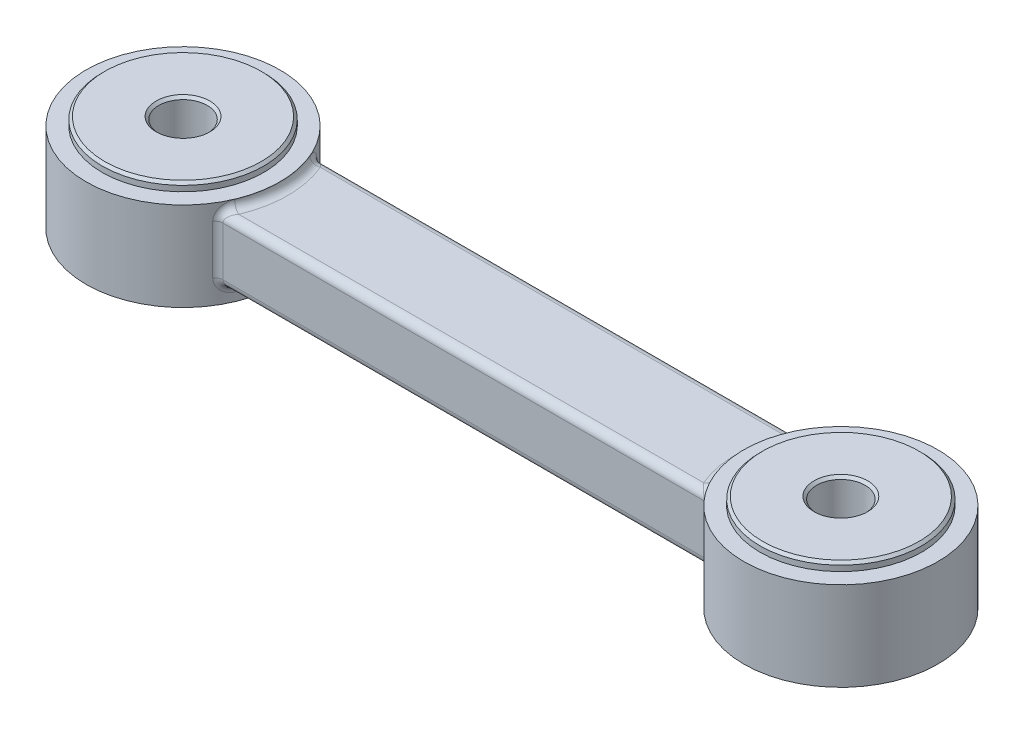
SolidWorks part; units mm, degrees
ref_plane "Front Plane" through (0, 0, 0) normal (0, 0, 1) x (1, 0, 0)
ref_plane "Top Plane" through (0, 0, 0) normal (0, 1, 0) x (1, 0, 0)
ref_plane "Right Plane" through (0, 0, 0) normal (1, 0, 0) x (0, 0, -1)
sketch "Sketch1" plane through (0, 0, 0) normal (0, 1, 0) x (1, 0, 0)
  circle A0 centre (0, 0) radius 19.05
  dimension "D1" = 38.1
extrude "Boss-Extrude2" add sketch "Sketch1" along normal blind 19.05
sketch "Sketch2" plane through (0, 0, 0) normal (0, 1, 0) x (1, 0, 0)
  circle A0 centre (129.2247, 0) radius 19.05
  dimension "D1" = 38.1
extrude "Boss-Extrude3" add sketch "Sketch2" along normal blind 19.05 separate body
sketch "Sketch3" plane through (0, 0, 0) normal (0, 1, 0) x (1, 0, 0)
  line L0 (19.05, 0) -> (110.1747, 0) construction
  line L1 (16.4978, 9.525) -> (112.7269, 9.525)
  line L2 (16.4978, -9.525) -> (112.7269, -9.525)
  circle A0 centre (0, 0) radius 19.05 construction
  circle A1 centre (129.2247, 0) radius 19.05 construction
  circle A3 centre (0, 0) radius 19.05
  arc A4 (16.4978, -9.525) -> (16.4978, 9.525) centre (0, 0) ccw
  circle A5 centre (129.2247, 0) radius 19.05
  arc A6 (112.7269, 9.525) -> (112.7269, -9.525) centre (129.2247, 0) ccw
  dimension "D3" = 9.525
  dimension "D1" = 0
  dimension "D2" = 0
extrude "Boss-Extrude4" add sketch "Sketch3" along normal blind 12.7 from offset 3.175
sketch "Sketch4" plane through (0, 19.05, 0) normal (0, 1, 0) x (1, 0, 0)
  circle A0 centre (0, 0) radius 15.875
  circle A1 centre (129.2247, 0) radius 15.875
  circle A3 centre (0, 0) radius 19.05
  circle A4 centre (0, 0) radius 19.05
  circle A5 centre (129.2247, 0) radius 19.05
  circle A6 centre (129.2247, 0) radius 19.05
  dimension "D1" = 31.75
  dimension "D2" = 31.75
  dimension "D3" = 0
  dimension "D4" = 0
extrude "Cut-Extrude1" cut sketch "Sketch4" against normal blind 1.6002
sketch "Sketch5" plane through (0, 19.05, 0) normal (0, 1, 0) x (1, 0, 0)
  circle A0 centre (0, 0) radius 4.7625
  circle A1 centre (129.2247, 0) radius 4.7625
  dimension "D1" = 9.525
  dimension "D2" = 9.525
extrude "Cut-Extrude2" cut sketch "Sketch5" against normal through all
fillet "Fillet1" radius 1.524 12 edges at (112.7269, 9.525, -9.525) (16.4978, 9.525, -9.525) (110.1747, 3.175, 0) (64.6123, 3.175, -9.525) (19.05, 3.175, 0) (16.4978, 9.525, 9.525) (112.7269, 9.525, 9.525) (64.6123, 3.175, 9.525) (64.6123, 15.875, -9.525) (110.1747, 15.875, 0) (64.6123, 15.875, 9.525) (19.05, 15.875, 0)
chamfer "Chamfer1" distance 0.508 angle 45 6 edges at (129.2247, 19.05, 4.7625) (129.2247, 0, 4.7625) (0, 19.05, 4.7625) (0, 0, 4.7625) (0, 19.05, 15.875) (129.2247, 19.05, 15.875)
